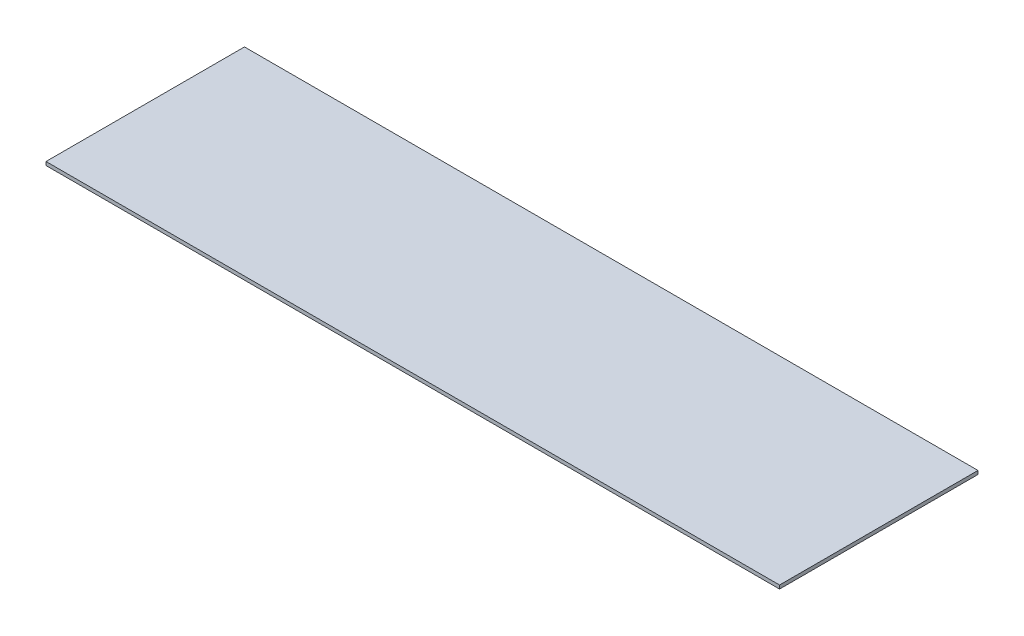
SolidWorks part; units mm, degrees
material "6061-T6 (SS)"
ref_plane "X-Y Datum" through (0, 0, 0) normal (0, 0, 1) x (1, 0, 0)
ref_plane "X-Z Datum" through (0, 0, 0) normal (0, 1, 0) x (1, 0, 0)
ref_plane "Y-Z Datum" through (0, 0, 0) normal (1, 0, 0) x (0, 0, -1)
sketch "Sketch1" plane through (0, 0, 0) normal (0, 1, 0) x (1, 0, 0)
  line L1 (-328.6176, 88.9) -> (328.6176, 88.9)
  line L2 (-328.6176, 88.9) -> (-328.6176, -88.9)
  line L3 (-328.6176, -88.9) -> (328.6176, -88.9)
  line L4 (328.6176, 88.9) -> (328.6176, -88.9)
  line L5 (-328.6176, 88.9) -> (328.6176, -88.9) construction
  line L6 (-328.6176, -88.9) -> (328.6176, 88.9) construction
  point P0 (0, 0)
  dimension "D1" = 657.2352
  dimension "D2" = 177.8
base flange "Base-Flange1" sketch "Sketch1" thickness 3.175 reverse thickness direction no parameters "D1"=1
sketch "Bend-Lines1" [suppressed] plane through (0, 0, 0) normal (0, 1, 0) x (1, 0, 0)
sketch "Bounding-Box1" [suppressed] plane through (0, 0, 0) normal (0, 1, 0) x (1, 0, 0)
sheet metal parameters "Sheet-Metal1" thickness 3.175 parameters "D1"=1
flat pattern "Flat-Pattern1" [suppressed]
sketch "Bend-Lines2" plane through (0, 0, 0) normal (0, 1, 0) x (1, 0, 0)
sketch3d "Bounding-Box2" [suppressed]
  line L0 (328.6176, -88.9, 0) -> (-328.6176, -88.9, 0) construction
  line L1 (328.6176, 88.9, 0) -> (-328.6176, 88.9, 0) construction
  line L2 (328.6176, -88.9, 0) -> (328.6176, 88.9, 0) construction
  line L3 (-328.6176, -88.9, 0) -> (-328.6176, 88.9, 0) construction
